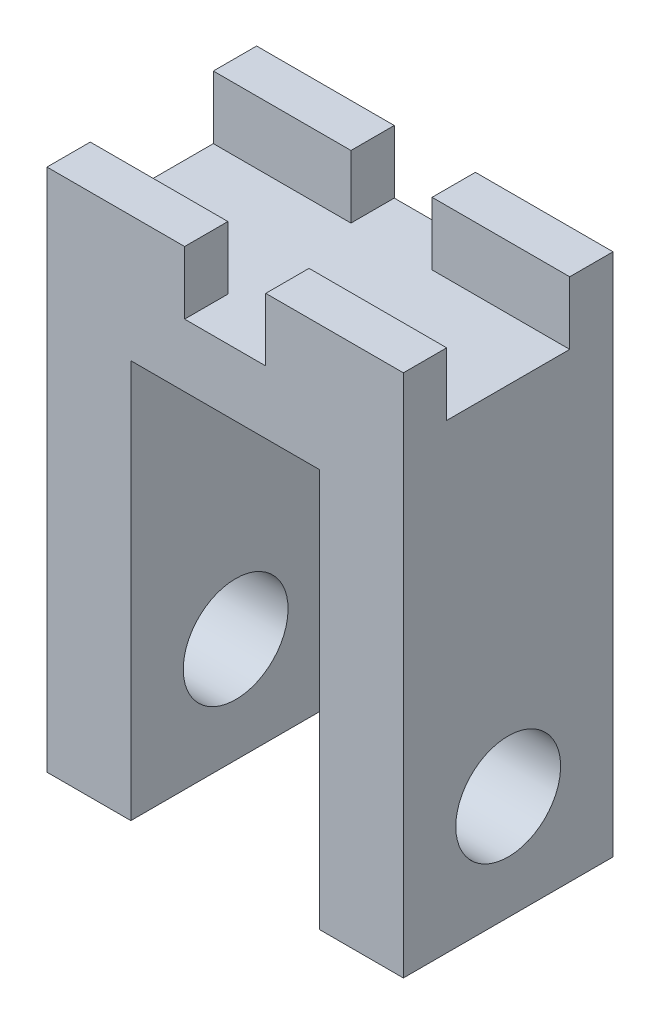
SolidWorks part; units mm, degrees
ref_plane "Front Plane" through (0, 0, 0) normal (0, 0, 1) x (1, 0, 0)
ref_plane "Top Plane" through (0, 0, 0) normal (0, 1, 0) x (1, 0, 0)
ref_plane "Right Plane" through (0, 0, 0) normal (1, 0, 0) x (0, 0, -1)
sketch "Sketch1" plane through (0, 0, 0) normal (0, 0, 1) x (1, 0, 0)
  line L1 (-4.5, 9.5) -> (4.5, 9.5)
  line L2 (-4.5, 9.5) -> (-4.5, -9.5)
  line L3 (-4.5, -9.5) -> (4.5, -9.5)
  line L4 (4.5, 9.5) -> (4.5, -9.5)
  line L5 (-4.5, 9.5) -> (4.5, -9.5) construction
  line L6 (-4.5, -9.5) -> (4.5, 9.5) construction
  line L7 (-8.5, 12.5) -> (8.5, 12.5)
  line L8 (-8.5, 12.5) -> (-8.5, -9.5)
  line L9 (-8.5, -9.5) -> (8.5, -9.5)
  line L10 (8.5, 12.5) -> (8.5, -9.5)
  point P0 (0, 0)
  point P10 (0, 12.5)
  point P11 (0, 9.5)
  dimension "D1" = 4
  dimension "D2" = 9
  dimension "D3" = 19
  dimension "D4" = 3
extrude "Boss-Extrude1" add sketch "Sketch1" along normal blind 10 contours L10 L7 L8 L9 L2 L1 L4 region at (-4.778, 0, 0)
sketch "Sketch2" plane through (-8.5, 0, 0) normal (-1, 0, 0) x (0, 0, 1)
  line L0 (10, 9.5) -> (0, 9.5) construction
  line L1 (10, 9.5) -> (0, 9.5)
  line L2 (10, -9.5) -> (0, -9.5) construction
  circle A0 centre (5, -4.5) radius 20 construction
  circle A1 centre (5, -4.5) radius 2.5
  point P6 (5, 9.5)
  dimension "D1" = 40
  dimension "D2" = 5
  dimension "D3" = 5
extrude "Cut-Extrude1" cut sketch "Sketch2" against normal through all both and the other way through all contours A1 region at (-8.5, -4.5, 5)
sketch "Sketch4" plane through (0, 12.5, 0) normal (0, 1, 0) x (1, 0, 0)
  line L0 (-1.935, -2.065) -> (1.935, -7.935) construction
  line L1 (-8.5, 0) -> (-1.935, 0)
  line L2 (-8.5, 0) -> (-8.5, -2.065)
  line L3 (-8.5, -2.065) -> (-1.935, -2.065)
  line L4 (-1.935, 0) -> (-1.935, -2.065)
  line L5 (-8.5, -10) -> (-1.935, -10)
  line L6 (-8.5, -10) -> (-8.5, -7.935)
  line L7 (-8.5, -7.935) -> (-1.935, -7.935)
  line L8 (-1.935, -10) -> (-1.935, -7.935)
  line L9 (8.5, 0) -> (1.935, 0)
  line L10 (8.5, 0) -> (8.5, -2.065)
  line L11 (8.5, -2.065) -> (1.935, -2.065)
  line L12 (1.935, 0) -> (1.935, -2.065)
  line L13 (8.5, -10) -> (1.935, -10)
  line L14 (8.5, -10) -> (8.5, -7.935)
  line L15 (8.5, -7.935) -> (1.935, -7.935)
  line L16 (1.935, -10) -> (1.935, -7.935)
  line L17 (-1.935, -7.935) -> (1.935, -2.065) construction
  point P19 (0, -5)
  dimension "D1" = 5.87
  dimension "D2" = 3.87
extrude "Boss-Extrude2" add sketch "Sketch4" along normal blind 3 contours L10 L9 L12 L11 | L2 L1 L4 L3 | L6 L5 L8 L7 | L14 L13 L16 L15
ref_axis "servoAxis" through (0, 12.5, 5) along (0, 1, 0)
